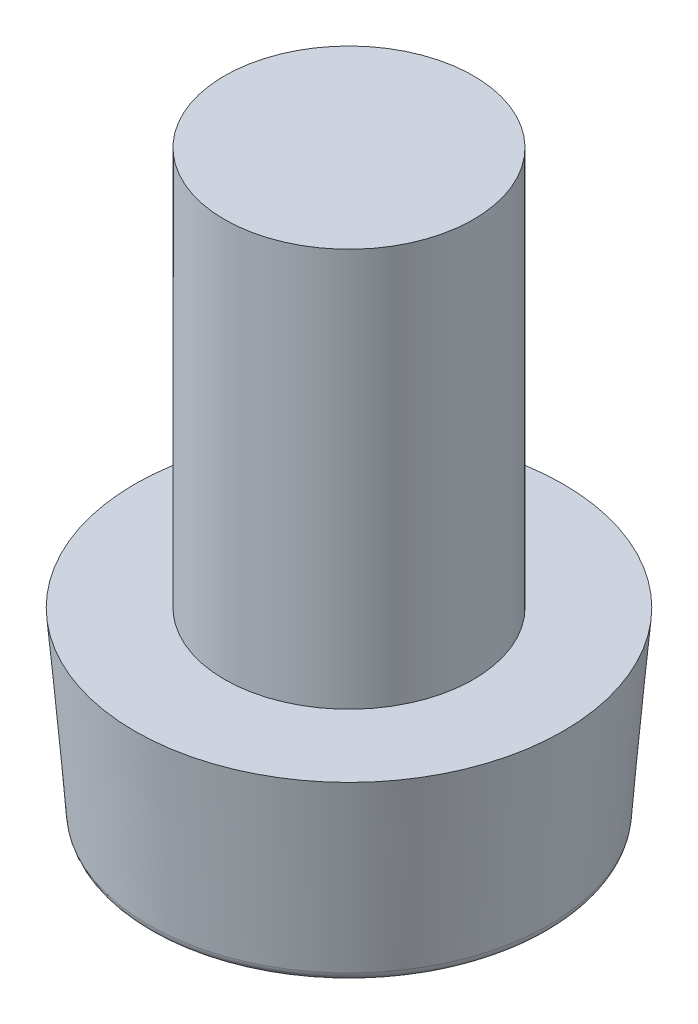
SolidWorks part; units mm, degrees
material "Nylon 101"
ref_plane "Plan de face" through (0, 0, 0) normal (0, 0, 1) x (1, 0, 0)
ref_plane "Plan de dessus" through (0, 0, 0) normal (0, 1, 0) x (1, 0, 0)
ref_plane "Plan de droite" through (0, 0, 0) normal (1, 0, 0) x (0, 0, -1)
sketch "Esquisse1" plane through (0, 0, 0) normal (0, 1, 0) x (1, 0, 0)
  circle A0 centre (0, 0) radius 2.15
  dimension "D1" = 4.3
extrude "Boss.-Extru.1" add sketch "Esquisse1" along normal blind 1.85
sketch "Esquisse2" plane through (0, 1.85, 0) normal (0, 1, 0) x (1, 0, 0)
  circle A0 centre (0, 0) radius 1.25
  dimension "D1" = 2.5
extrude "Boss.-Extru.2" add sketch "Esquisse2" along normal blind 4
chamfer "Chanfrein1" distance 0.15 distance2 1.85 1 edges at (0, 0, 2.15) first distance on face at (0, 0, 2.15)
fillet "Congé1" radius 0.1 1 edges at (0, 0, 2)
